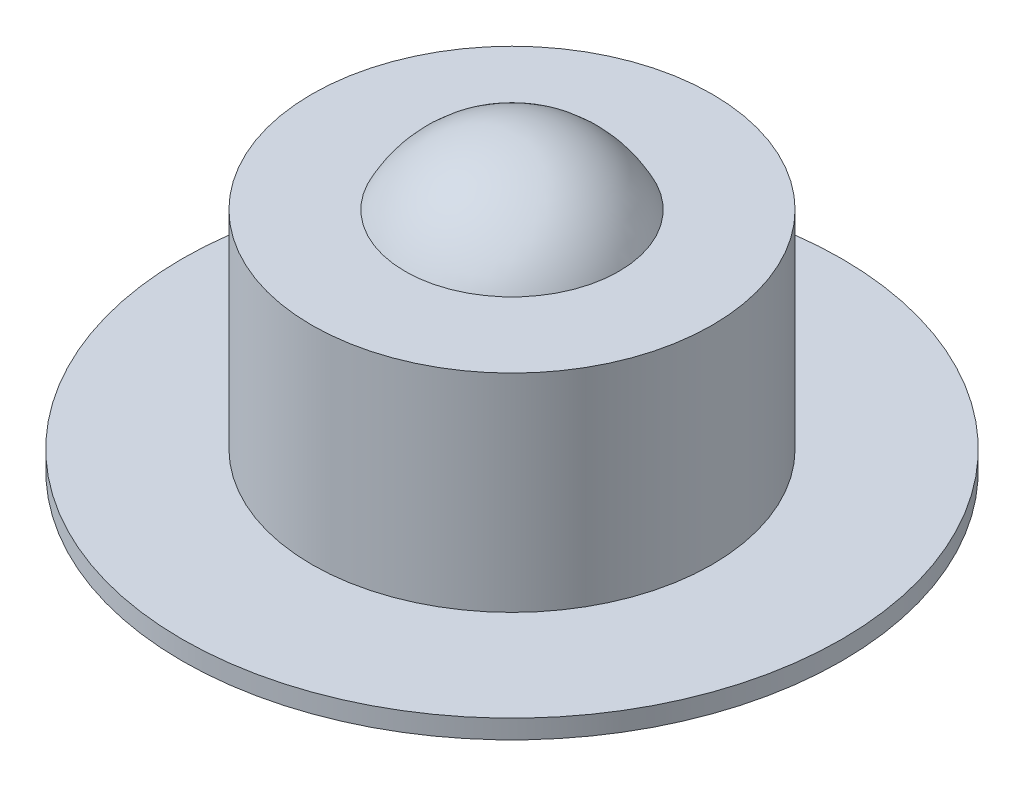
SolidWorks part; units mm, degrees
material "普通碳钢"
ref_plane "前视基准面" through (0, 0, 0) normal (0, 0, 1) x (1, 0, 0)
ref_plane "上视基准面" through (0, 0, 0) normal (0, 1, 0) x (1, 0, 0)
ref_plane "右视基准面" through (0, 0, 0) normal (1, 0, 0) x (0, 0, -1)
sketch "草图1" plane through (0, 0, 0) normal (0, 1, 0) x (1, 0, 0)
  circle A0 centre (0, 0) radius 35
  circle A1 centre (0, 0) radius 21.25
  dimension "D1" = 70
  dimension "D2" = 42.5
extrude "凸台-拉伸1" add sketch "草图1" along normal blind 2 contours A1 | A0 A1 region at (-34.0101, 0, 0) region at (0, 0, 0)
extrude "凸台-拉伸2" add sketch "草图1<3>" along normal blind 24 contours A1 region at (0, 0, 0)
sketch "草图1<3>" plane through (0, 0, 0) normal (0, 1, 0) x (1, 0, 0) same geometry as "草图1"
sketch "草图2" plane through (0, 0, 0) normal (0, 0, 1) x (1, 0, 0)
  line L0 (-1000, 18.3) -> (49000, 18.3) construction
  line L2 (21.25, 24) -> (-21.25, 24) construction
  circle A0 centre (0, 18.3) radius 12.7
  point P2 (0, 31)
  dimension "D1" = 25.4
  dimension "D2" = 7
revolve "旋转1" add sketch "草图2" angle 360 about L0 region at (0, 23.69, 0)
